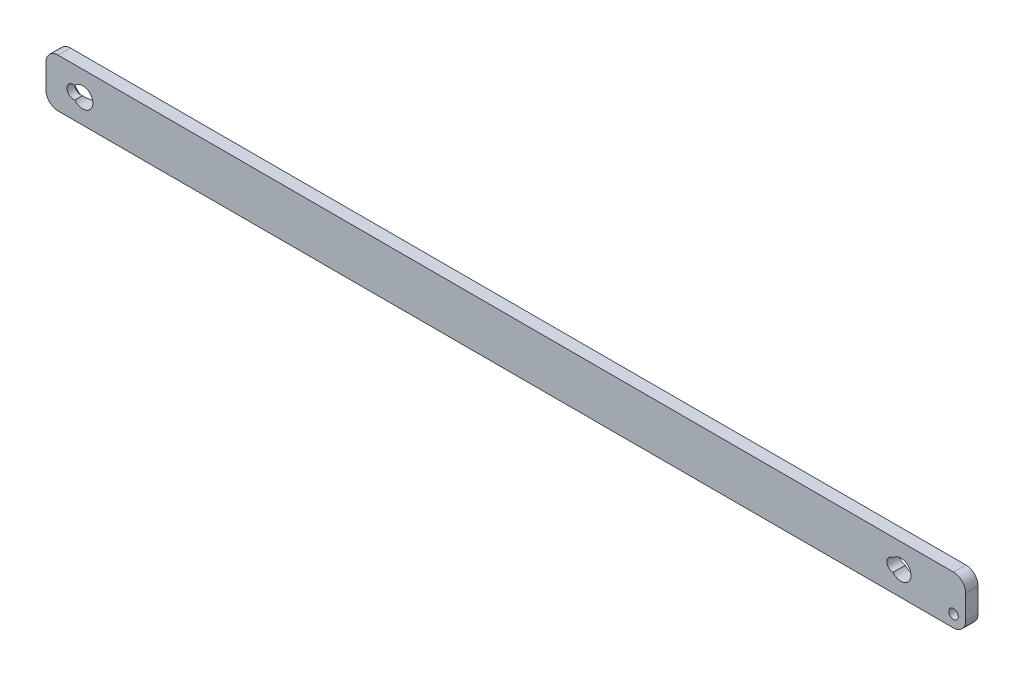
SolidWorks part; units mm, degrees
material "PC High Viscosity"
ref_plane "Front Plane" through (0, 0, 0) normal (0, 0, 1) x (1, 0, 0)
ref_plane "Top Plane" through (0, 0, 0) normal (0, 1, 0) x (1, 0, 0)
ref_plane "Right Plane" through (0, 0, 0) normal (1, 0, 0) x (0, 0, -1)
sketch "Sketch1" plane through (0, 0, 0) normal (0, 0, 1) x (1, 0, 0)
  line L1 (0, 0) -> (40.5308, 0)
  line L2 (0, 0) -> (0, 25.4)
  line L3 (0, 25.4) -> (40.5307, 25.4)
  line L4 (482.6, 0) -> (482.6, 25.4)
  line L11 (482.6, 10.0162) -> (476.25, 13.6823) construction
  line L12 (476.25, 13.6823) -> (469.9, 10.0162) construction
  line L13 (469.9, 10.0162) -> (469.9, 2.6838) construction
  line L14 (469.9, 2.6838) -> (476.25, -0.9823) construction
  line L15 (476.25, -0.9823) -> (482.6, 2.6838) construction
  line L16 (482.6, 2.6838) -> (482.6, 10.0162) construction
  line L22 (40.5307, 25.4) -> (482.6, 25.4)
  line L23 (40.5308, 0) -> (343.7103, 0)
  line L24 (343.7103, 0) -> (482.6, 0)
  circle A0 centre (476.25, 6.35) radius 2.4892
  circle A1 centre (476.25, 6.35) radius 6.35 construction
  circle A2 centre (448.6421, 12.7) radius 5.2837
  circle A3 centre (19.3196, 12.7) radius 5.2837
  point P11 (0, 0)
  point P12 (0, 12.7)
  dimension "D5" = 4.9784
  dimension "D7" = 12.7
  dimension "D1" = 482.6
  dimension "D2" = 25.4
extrude "Boss-Extrude1" add sketch "Sketch1" along normal blind 6.477 contours L3 | L1 L4 L3 L2 A0 | L1 region at (241.0273, 12.7102, 0)
fillet "Fillet2" radius 6.35 4 edges at (482.6, 25.4, 3.2385) (482.6, 0, 3.2385) (0, 0, 3.2385) (0, 25.4, 3.2385)
sketch "Sketch2" plane through (0, 0, 6.477) normal (0, 0, 1) x (1, 0, 0)
  line L2 (482.6, 6.35) -> (482.6, 19.05) construction
  line L3 (6.35, 25.4) -> (476.25, 25.4) construction
  circle A0 centre (444.5, 12.7) radius 3.2639
  dimension "D1" = 6.5278
  dimension "D2" = 12.7
  dimension "D3" = 38.1
mirror "Mirror2" about plane through (0, 0, 0) normal (0, 0, 1) of bodies 101 108
delete or keep bodies "Body-Delete/Keep 1" type delete bodies bodies 101
fillet "Fillet3" radius 3.175 rebuild error yes
extrude "Cut-Extrude1" cut sketch "Sketch2" against normal through all
hole_wizard "CSK for 1/4 Flat Head Machine Screw (100)1" positions "Sketch3" profile "Sketch4" countersink size "1/4" standard "ANSI Inch"
sketch "Sketch3" plane through (0, 0, -6.477) normal (0, 0, 1) x (1, 0, 0)
  line L0 (6.35, 0) -> (476.25, 0) construction
  line L1 (0, 6.35) -> (0, 19.05) construction
  point P0 (14.3939, 12.7)
  dimension "D1" = 12.7
  dimension "D2" = 14.3939
sketch "Sketch4" plane through (14.3939, 12.7, -6.477) normal (1, 0, 0) x (0, 1, 0)
  line L0 (0, 0) -> (0, 21.0798)
  line L1 (0, 21.0798) -> (3.3782, 19.05)
  line L2 (3.3782, 19.05) -> (3.3782, 2.5682)
  line L3 (3.3782, 2.5682) -> (6.4389, 0)
  line L5 (6.4389, 0) -> (0, 0)
  line L6 (-3.3782, 2.5682) -> (-6.4389, 0) construction
  line L10 (0, 21.0798) -> (-3.3782, 19.05) construction
  line L11 (0, -6.35) -> (0, 107.95) construction
  dimension "Hole Dia." = 6.7564
  dimension "Hole Depth" = 19.05
  dimension "Near C'Sink Dia." = 12.8778
  dimension "Near C'Sink Angle" = 100
  dimension "Drill Angle" = 118
